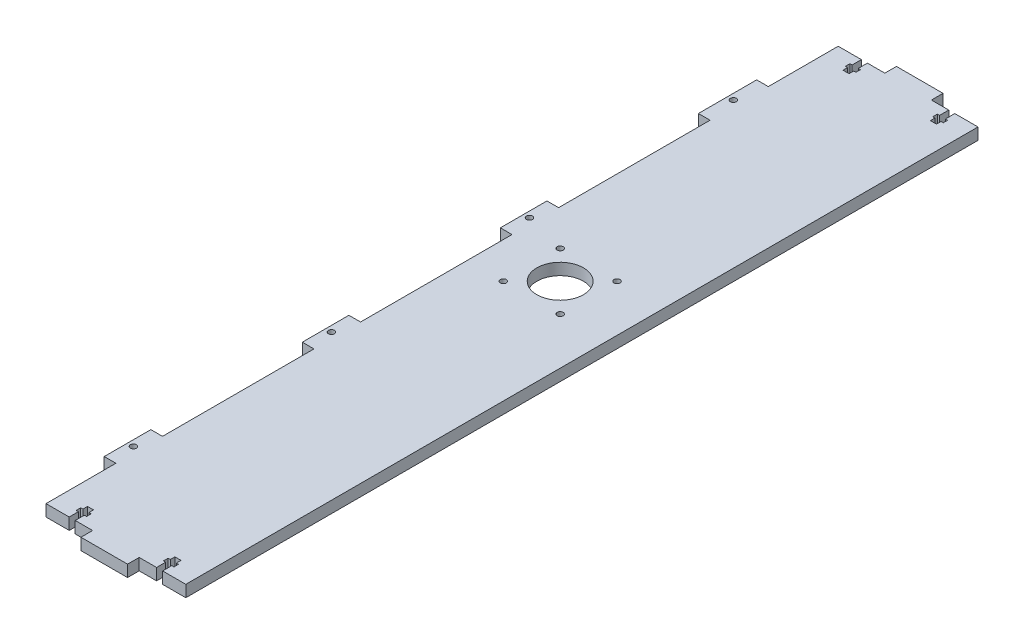
SolidWorks part; units mm, degrees
material "Pine"
ref_plane "Front Plane" through (0, 0, 0) normal (0, 0, 1) x (1, 0, 0)
ref_plane "Top Plane" through (0, 0, 0) normal (0, 1, 0) x (1, 0, 0)
ref_plane "Right Plane" through (0, 0, 0) normal (1, 0, 0) x (0, 0, -1)
ref_plane "Plane1" through (0, 50.8, 0) normal (0, -1, 0) x (1, 0, 0)
sketch "Sketch1" plane through (0, 50.8, 0) normal (0, -1, 0) x (1, 0, 0)
  line L0 (-350.52, 222.25) -> (-350.52, 215.9)
  line L1 (-350.52, 215.9) -> (-359.9825, 215.9)
  line L2 (-359.9825, 215.9) -> (-359.9825, 210.9)
  line L3 (-359.9825, 210.9) -> (-358.7825, 210.9)
  line L4 (-358.7825, 210.9) -> (-358.7825, 208.4)
  line L5 (-358.7825, 208.4) -> (-359.9825, 208.4)
  line L6 (-359.9825, 208.4) -> (-359.9825, 205.9)
  line L7 (-359.9825, 205.9) -> (-363.2825, 205.9)
  line L8 (-363.2825, 205.9) -> (-363.2825, 208.4)
  line L9 (-363.2825, 208.4) -> (-364.4825, 208.4)
  line L10 (-364.4825, 208.4) -> (-364.4825, 210.9)
  line L11 (-364.4825, 210.9) -> (-363.2825, 210.9)
  line L12 (-363.2825, 210.9) -> (-363.2825, 215.9)
  line L13 (-363.2825, 215.9) -> (-375.92, 215.9)
  line L14 (-375.92, 215.9) -> (-375.92, 177.8)
  line L15 (-375.92, 177.8) -> (-382.27, 177.8)
  line L16 (-382.27, 177.8) -> (-382.27, 152.4)
  line L17 (-382.27, 152.4) -> (-375.92, 152.4)
  line L18 (-375.92, 152.4) -> (-375.92, 69.85)
  line L19 (-375.92, 69.85) -> (-382.27, 69.85)
  line L20 (-382.27, 69.85) -> (-382.27, 44.45)
  line L21 (-382.27, 44.45) -> (-375.92, 44.45)
  line L22 (-375.92, 44.45) -> (-375.92, -38.1)
  line L23 (-375.92, -38.1) -> (-382.27, -38.1)
  line L24 (-382.27, -38.1) -> (-382.27, -63.5)
  line L25 (-382.27, -63.5) -> (-375.92, -63.5)
  line L26 (-375.92, -63.5) -> (-375.92, -146.05)
  line L27 (-375.92, -146.05) -> (-382.27, -146.05)
  line L28 (-382.27, -146.05) -> (-382.27, -177.8)
  line L29 (-382.27, -177.8) -> (-375.92, -177.8)
  line L30 (-375.92, -177.8) -> (-375.92, -215.9)
  line L31 (-375.92, -215.9) -> (-363.2825, -215.9)
  line L32 (-363.2825, -215.9) -> (-363.2825, -210.9)
  line L33 (-363.2825, -210.9) -> (-364.4825, -210.9)
  line L34 (-364.4825, -210.9) -> (-364.4825, -208.4)
  line L35 (-364.4825, -208.4) -> (-363.2825, -208.4)
  line L36 (-363.2825, -208.4) -> (-363.2825, -205.9)
  line L37 (-363.2825, -205.9) -> (-359.9825, -205.9)
  line L38 (-359.9825, -205.9) -> (-359.9825, -208.4)
  line L39 (-359.9825, -208.4) -> (-358.7825, -208.4)
  line L40 (-358.7825, -208.4) -> (-358.7825, -210.9)
  line L41 (-358.7825, -210.9) -> (-359.9825, -210.9)
  line L42 (-359.9825, -210.9) -> (-359.9825, -215.9)
  line L43 (-359.9825, -215.9) -> (-350.52, -215.9)
  line L44 (-350.52, -215.9) -> (-350.52, -222.25)
  line L45 (-350.52, -222.25) -> (-325.12, -222.25)
  line L46 (-325.12, -222.25) -> (-325.12, -215.9)
  line L47 (-325.12, -215.9) -> (-315.6575, -215.9)
  line L48 (-315.6575, -215.9) -> (-315.6575, -210.9)
  line L49 (-315.6575, -210.9) -> (-316.8575, -210.9)
  line L50 (-316.8575, -210.9) -> (-316.8575, -208.4)
  line L51 (-316.8575, -208.4) -> (-315.6575, -208.4)
  line L52 (-315.6575, -208.4) -> (-315.6575, -205.9)
  line L53 (-315.6575, -205.9) -> (-312.3575, -205.9)
  line L54 (-312.3575, -205.9) -> (-312.3575, -208.4)
  line L55 (-312.3575, -208.4) -> (-311.1575, -208.4)
  line L56 (-311.1575, -208.4) -> (-311.1575, -210.9)
  line L57 (-311.1575, -210.9) -> (-312.3575, -210.9)
  line L58 (-312.3575, -210.9) -> (-312.3575, -215.9)
  line L59 (-312.3575, -215.9) -> (-299.72, -215.9)
  line L60 (-299.72, -215.9) -> (-299.72, 215.9)
  line L61 (-299.72, 215.9) -> (-312.3575, 215.9)
  line L62 (-312.3575, 215.9) -> (-312.3575, 210.9)
  line L63 (-312.3575, 210.9) -> (-311.1575, 210.9)
  line L64 (-311.1575, 210.9) -> (-311.1575, 208.4)
  line L65 (-311.1575, 208.4) -> (-312.3575, 208.4)
  line L66 (-312.3575, 208.4) -> (-312.3575, 205.9)
  line L67 (-312.3575, 205.9) -> (-315.6575, 205.9)
  line L68 (-315.6575, 205.9) -> (-315.6575, 208.4)
  line L69 (-315.6575, 208.4) -> (-316.8575, 208.4)
  line L70 (-316.8575, 208.4) -> (-316.8575, 210.9)
  line L71 (-316.8575, 210.9) -> (-315.6575, 210.9)
  line L72 (-315.6575, 210.9) -> (-315.6575, 215.9)
  line L73 (-315.6575, 215.9) -> (-325.12, 215.9)
  line L74 (-325.12, 215.9) -> (-325.12, 222.25)
  line L75 (-325.12, 222.25) -> (-350.52, 222.25)
  circle A0 centre (-379.095, 165.1) radius 1.65
  circle A1 centre (-379.095, 57.15) radius 1.65
  circle A2 centre (-379.095, -161.925) radius 1.65
  circle A3 centre (-379.095, -50.8) radius 1.65
  circle A4 centre (-325.259, -13.6883) radius 1.65
  circle A5 centre (-356.259, -13.6883) radius 1.65
  circle A6 centre (-325.259, -44.6883) radius 1.65
  circle A7 centre (-356.259, -44.6883) radius 1.65
  circle A8 centre (-340.759, -29.1883) radius 12.7
extrude "Boss-Extrude1" add sketch "Sketch1" against normal blind 6.35
